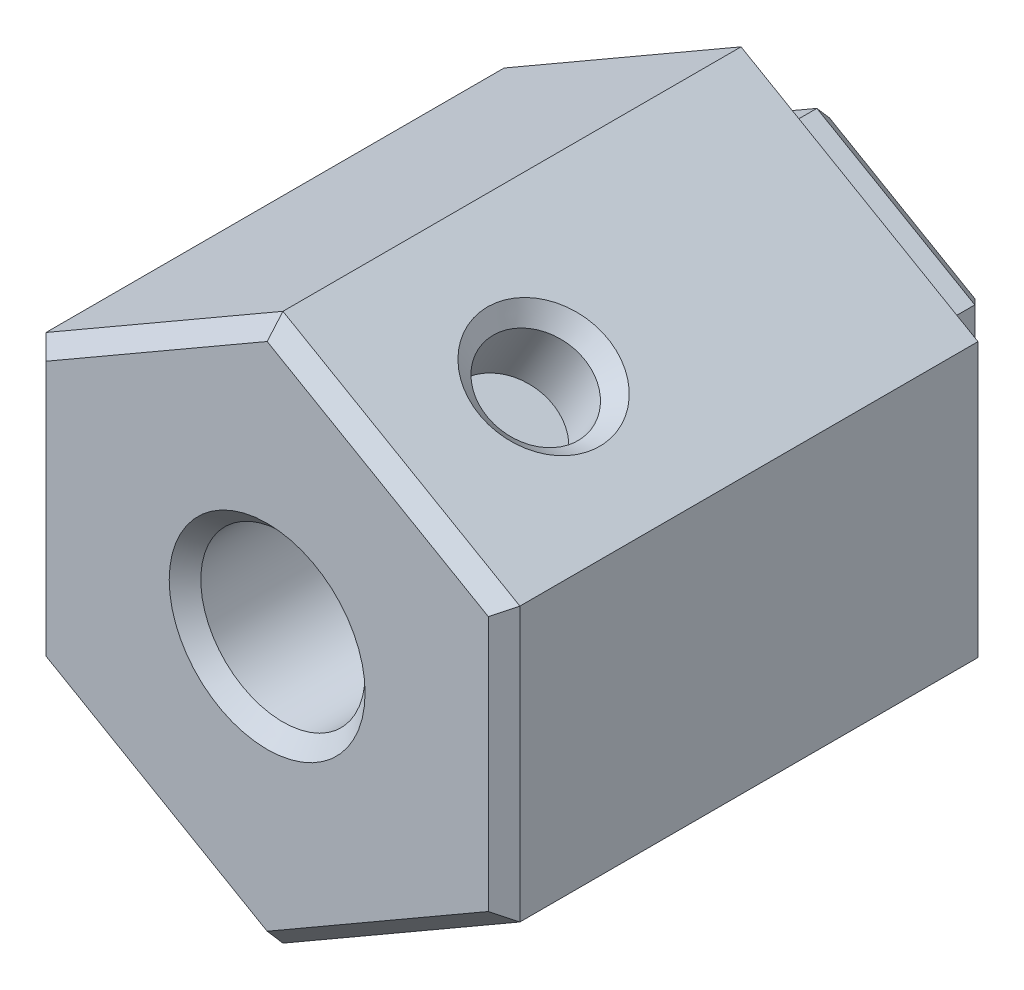
SolidWorks part; units mm, degrees
ref_plane "Front" through (0, 0, 0) normal (0, 0, 1) x (1, 0, 0)
ref_plane "Top" through (0, 0, 0) normal (0, 1, 0) x (1, 0, 0)
ref_plane "Right" through (0, 0, 0) normal (1, 0, 0) x (0, 0, -1)
sketch "Sketch1" plane through (0, 0, 0) normal (0, 0, 1) x (1, 0, 0)
  line L1 (0, 8.6603) -> (-7.5, 4.3301)
  line L2 (-7.5, 4.3301) -> (-7.5, -4.3301)
  line L3 (-7.5, -4.3301) -> (0, -8.6603)
  line L4 (0, -8.6603) -> (7.5, -4.3301)
  line L5 (7.5, -4.3301) -> (7.5, 4.3301)
  line L6 (7.5, 4.3301) -> (0, 8.6603)
  circle A0 centre (0, 0) radius 7.5 construction
  dimension "D1" = 15
extrude "Boss-Extrude1" add sketch "Sketch1" along normal blind 15
sketch "Sketch3" plane through (0, 0, 0) normal (0, 0, -1) x (-1, 0, 0)
  line L0 (-7.5, 4.3301) -> (0, 8.6603) construction
  line L1 (0, 5.7735) -> (-5, 2.8868)
  line L2 (-5, 2.8868) -> (-5, -2.8868)
  line L3 (-5, -2.8868) -> (0, -5.7735)
  line L4 (0, -5.7735) -> (5, -2.8868)
  line L5 (5, -2.8868) -> (5, 2.8868)
  line L6 (5, 2.8868) -> (0, 5.7735)
  circle A0 centre (0, 0) radius 5 construction
  dimension "D1" = 10
extrude "Boss-Extrude2" add sketch "Sketch3" along normal blind 2.8
sketch "Sketch2" plane through (0, 0, 15) normal (0, 0, 1) x (1, 0, 0)
  circle A0 centre (0, 0) radius 2.6
  dimension "D1" = 5.2
extrude "Cut-Extrude1" cut sketch "Sketch2" against normal through all
sketch "Sketch4" plane through (3.75, 6.4952, 0) normal (0.5, 0.866, 0) x (0.866, -0.5, 0)
  line L0 (4.3301, 0) -> (-4.3301, 0) construction
  circle A0 centre (0, -10) radius 1.55
  point P5 (0, 0)
  dimension "D1" = 3.1
  dimension "D2" = 10
extrude "Cut-Extrude3" cut sketch "Sketch4" against normal blind 2.5
ref_axis "Axis1" through (0, 0, -2.8) along (0, 0, 1)
pattern_circular "CirPattern1" count 3 over 360 about axis through (0, 0, 15) along (0, 0, 1) of "Cut-Extrude3"
chamfer "Chamfer1" distance 0.5 angle 45 7 edges at (7.5, 0, 15) (3.75, -6.4952, 15) (-3.75, -6.4952, 15) (-7.5, 0, 15) (-3.75, 6.4952, 15) (3.75, 6.4952, 15) (2.6, 0, 15)
chamfer "Chamfer2" distance 0.5 angle 45 3 edges at (-7.5, -1.55, 10) (5.0923, -5.7202, 10) (2.4077, 7.2702, 10)
chamfer "Chamfer3" distance 1 angle 45 1 edges at (2.6, 0, -2.8)
chamfer "Chamfer4" distance 0.4 angle 45 6 edges at (-5, 0, -2.8) (-2.5, -4.3301, -2.8) (2.5, -4.3301, -2.8) (5, 0, -2.8) (2.5, 4.3301, -2.8) (-2.5, 4.3301, -2.8)
